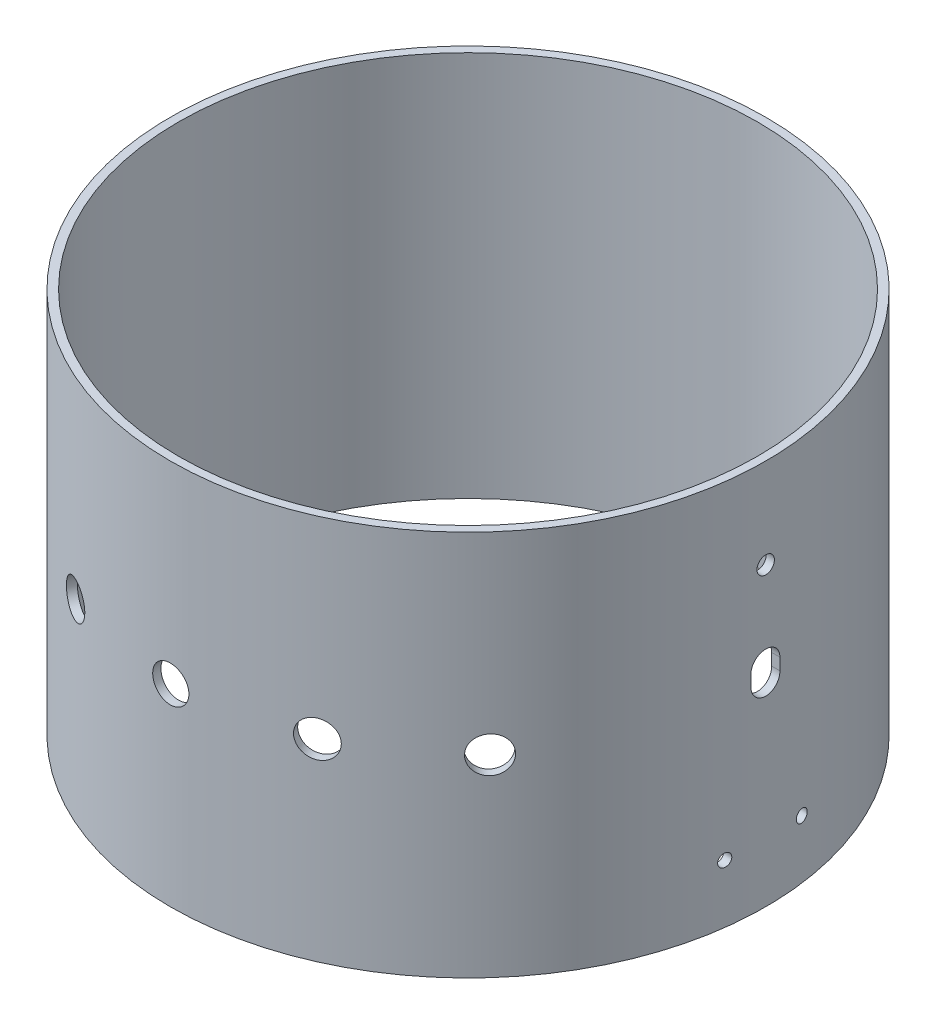
SolidWorks part; units mm, degrees
material "C-Glass Fiber"
ref_plane "Front Plane" through (0, 0, 0) normal (0, 0, 1) x (1, 0, 0)
ref_plane "Top Plane" through (0, 0, 0) normal (0, 1, 0) x (1, 0, 0)
ref_plane "Right Plane" through (0, 0, 0) normal (1, 0, 0) x (0, 0, -1)
sketch "Body Tube Profile" plane through (0, 0, 0) normal (0, 1, 0) x (1, 0, 0)
  circle A0 centre (0, 0) radius 76.2
  circle A1 centre (0, 0) radius 78.359
  dimension "D1" = 152.4
  dimension "D2" = 156.718
extrude "Body Tube Extrustion" add sketch "Body Tube Profile" along normal blind 101.6
ref_plane "Plane1" through (0, 0, 78.359) normal (0, 0, 1) x (1, 0, 0)
sketch "Sketch1" plane through (0, 0, 78.359) normal (0, 0, 1) x (1, 0, 0)
  line L0 (0, 0) -> (0, 101.6) construction
  line L1 (78.359, 101.6) -> (-78.359, 101.6) construction
  point P5 (0, 50.8)
hole_wizard "3/8 (0.375) Diameter Hole1" positions "Sketch1" profile "Sketch2" hole size "3/8" standard "ANSI Inch" end condition up to next
sketch "Sketch2" plane through (0, 50.8, 78.359) normal (1, 0, 0) x (0, -1, 0)
  line L0 (0, 0) -> (0, 2.159)
  line L1 (0, 2.159) -> (4.7625, 2.159)
  line L2 (4.7625, 2.159) -> (4.7625, 0)
  line L5 (4.7625, 0) -> (0, 0)
  line L11 (0, -6.35) -> (0, 107.95) construction
  dimension "Thru Hole Dia." = 9.525
  dimension "Thru Hole Depth" = 2.159
pattern_circular "CirPattern1" count 3 every 24 about axis through (0, 101.6, 0) along (0, 1, 0) of "3/8 (0.375) Diameter Hole1" other way count 3
ref_plane "Plane2" through (78.359, 0, 0) normal (1, 0, 0) x (0, 0, -1)
sketch "Sketch4" plane through (78.359, 0, 0) normal (1, 0, 0) x (0, 0, -1)
  line L0 (0, 101.6) -> (0, 0) construction
  line L1 (78.359, 101.6) -> (-78.359, 101.6) construction
  line L5 (-16.24, 91.4193) -> (16.24, 91.4193) construction
  line L6 (-16.24, 91.4193) -> (-16.24, 10.1807) construction
  line L7 (-16.24, 10.1807) -> (16.24, 10.1807) construction
  line L8 (16.24, 91.4193) -> (16.24, 10.1807) construction
  circle A0 centre (10.1395, 15.368) radius 1.651
  circle A1 centre (-10.1395, 15.368) radius 1.651
  circle A2 centre (0, 77.9499) radius 2.286
  point P5 (-10.1395, 15.368)
  point P6 (10.1395, 15.368)
  point P9 (0, 77.9499)
  dimension "D4" = 3.302
  dimension "D5" = 4.572
  dimension "D1" = 10.1395
  dimension "D2" = 10.1395
  dimension "D3" = 62.5819
  dimension "D6" = 5.1873
  dimension "D7" = 13.4694
  dimension "D8" = 6.1005
  dimension "D9" = 6.1005
  dimension "D10" = 10.1807
extrude "Cut-Extrude1" cut sketch "Sketch4" against normal up to next
sketch "Sketch5" plane through (78.359, 0, 0) normal (1, 0, 0) x (0, 0, -1)
  line L0 (0, 0) -> (0, 101.6) construction
  line L1 (76.2, 101.6) -> (-76.2, 101.6) construction
  line L2 (-3.81, 54.9376) -> (-3.81, 51.834)
  line L3 (3.81, 54.9376) -> (3.81, 51.834)
  line L4 (-10.1395, 15.368) -> (10.1395, 15.368) construction
  circle A0 centre (0, 54.9376) radius 3.81
  circle A1 centre (0, 51.834) radius 3.81
  dimension "D2" = 7.62
  dimension "D1" = 3.1036
  dimension "D3" = 36.466
extrude "Cut-Extrude2" cut sketch "Sketch5" against normal up to next contours L0 A1 A0 | A1 L0 A0 | A0 L0 A1 | L0 A0 A1 | A1 L3 A0 | A1 A0 L2 | A1 region at (78.359, 53.3858, 3.7117) region at (78.359, 56.4656, 0) region at (78.359, 53.3858, -3.7117) region at (78.359, 53.3858, 0)
equation "\"Length\"=4"
equation "\"Outer Diameter\"= 6.17"
equation "\"Inner Diameter\"= 6"
equation "\"Wall Thickness\"= 0.085"
equation "\"D1@Body Tube Profile\" = \"Inner Diameter\""
equation "\"D2@Body Tube Profile\" = \"Outer Diameter\""
equation "\"D1@Body Tube Extrustion\" = \"Length\""
equation "\"Key Hole Dia\"=0.375"
equation "\"Hole Angle 1\"= 15"
equation "\"Hole Angle 2\"= 45"
equation "\"D10@Sketch4\"=(4-3.19837298)/2"
